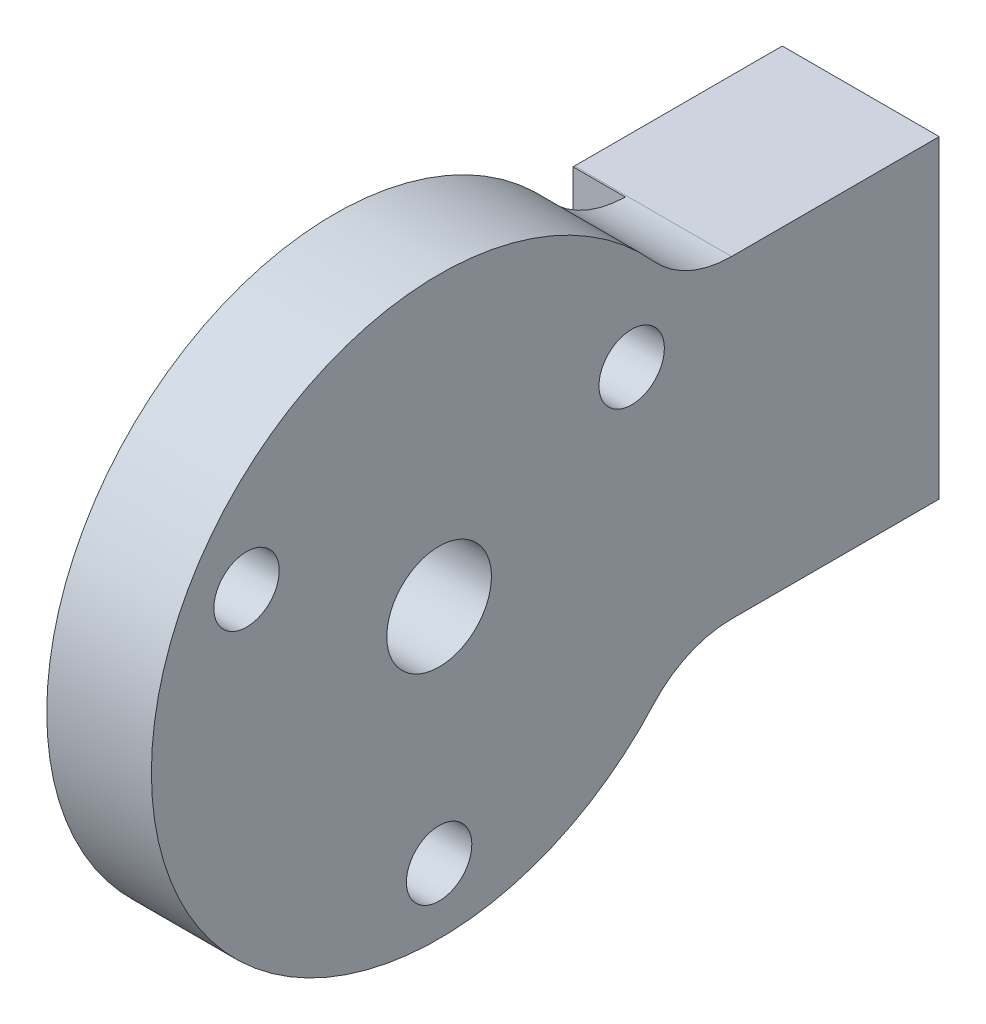
SolidWorks part; units mm, degrees
ref_plane "Front" through (0, 0, 0) normal (0, 0, 1) x (1, 0, 0)
ref_plane "Top" through (0, 0, 0) normal (0, 1, 0) x (1, 0, 0)
ref_plane "Right" through (0, 0, 0) normal (1, 0, 0) x (0, 0, -1)
sketch "Sketch1" plane through (0, 0, 0) normal (0, 0, 1) x (1, 0, 0)
  line L1 (-4, 6) -> (2, 6)
  line L2 (-4, 6) -> (-4, -6)
  line L3 (-4, -6) -> (2, -6)
  line L4 (2, 6) -> (2, -6)
  dimension "D1" = 6
  dimension "D2" = 6
  dimension "D3" = 4
  dimension "D4" = 2
extrude "Extrude1" add sketch "Sketch1" along normal blind 8
sketch "Sketch2" plane through (0, 0, 0) normal (0, 0, -1) x (-1, 0, 0)
  line L0 (-2, 6) -> (4, 6) construction
  line L1 (4, -6) -> (-2, -6) construction
  line L2 (4, 6) -> (4, -6) construction
  circle A0 centre (1, 3) radius 1.25
  circle A1 centre (1, -3) radius 1.25
  dimension "D2" = 2.5
  dimension "D3" = 2.5
  dimension "D1" = 3
  dimension "D4" = 3
  dimension "D5" = 3
sketch "Sketch3" plane through (0, 0, 8) normal (0, 0, 1) x (1, 0, 0)
  line L1 (-2, 4.3) -> (2, 4.3)
  line L2 (-2, 4.3) -> (-2, -4.3)
  line L3 (-2, -4.3) -> (2, -4.3)
  line L4 (2, 4.3) -> (2, -4.3)
  dimension "D1" = 2
  dimension "D2" = 2
  dimension "D3" = 4.3
  dimension "D4" = 4.3
extrude "Extrude2" add sketch "Sketch3" along normal blind 1
extrude "Extrude3" cut sketch "Sketch2" against normal blind 6
cosmetic thread "Hole Thread1" parameters "D1"=4.5, "D2"=3
cosmetic thread "Hole Thread2" parameters "D1"=4.5, "D2"=3
sketch "Sketch4" plane through (2, 0, 0) normal (1, 0, 0) x (0, 0, -1)
  line L0 (-9.9005, 6) -> (-8, 6)
  line L1 (-9, -4.3) -> (-9, 4.3) construction
  line L2 (-8, 6) -> (-8, -6)
  line L3 (-8, -6) -> (-9.9005, -6)
  arc A0 (-9.9005, 6) -> (-9.9005, -6) centre (-19.12, 0) ccw
  dimension "D2" = 11
  dimension "D1" = 10.12
extrude "Extrude4" add sketch "Sketch4" against normal blind 4
sketch "Sketch6" plane through (-2, 0, 0) normal (-1, 0, 0) x (0, 0, 1)
  circle A0 centre (19.12, 0) radius 5.25
  dimension "D1" = 10.5
extrude "Extrude5" cut sketch "Sketch6" against normal blind 1
ref_axis "Axis1" through (-1, 0, 19.12) along (-1, 0, 0)
sketch "Sketch7" plane through (-2, 0, 0) normal (-1, 0, 0) x (0, 0, 1)
  circle A0 centre (19.12, -8.5) radius 1.25
  circle A1 centre (19.12, 0) radius 5.25 construction
  dimension "D1" = 2.5
  dimension "D2" = 8.5
extrude "Extrude6" cut sketch "Sketch7" against normal up to surface (4 mm away) up to face at (2, 0, 10.0051)
pattern_circular "CirPattern1" count 3 over 360 about axis through (-1, 0, 19.12) along (-1, 0, 0) of "Extrude6"
sketch "Sketch8" plane through (-1, 0, 0) normal (-1, 0, 0) x (0, 0, 1)
  circle A0 centre (19.12, 0) radius 2
  dimension "D1" = 4
extrude "Extrude7" cut sketch "Sketch8" against normal up to surface (3 mm away) up to face at (2, 3, 11.7588)
fillet "Fillet1" radius 4 2 edges at (0, 6, 9.9005) (0, -6, 9.9005)
hole_wizard "M3 Tapped Hole1" positions "3DSketch1" profile "Sketch9" tap size "M3" standard "DIN"
sketch3d "3DSketch1"
  line L0 (-1, 3, 6) -> (-1, 3, 0) construction
  line L1 (-1, -3, 6) -> (-1, -3, 0) construction
  point P0 (-1, 3, 0)
  point P4 (-1, -3, 0)
sketch "Sketch9" plane through (-1, 3, 0) normal (1, 0, 0) x (0, 1, 0)
  line L0 (0, 0) -> (0, 6.7511)
  line L1 (0, 6.7511) -> (1.25, 6)
  line L2 (1.25, 6) -> (1.25, 0)
  line L5 (1.25, 0) -> (0, 0)
  line L10 (0, 6.7511) -> (-1.25, 6) construction
  line L11 (0, -6.35) -> (0, 107.95) construction
  dimension "Tap Drill Dia." = 2.5
  dimension "Tap Drill Depth" = 6
  dimension "Drill Angle" = 118
